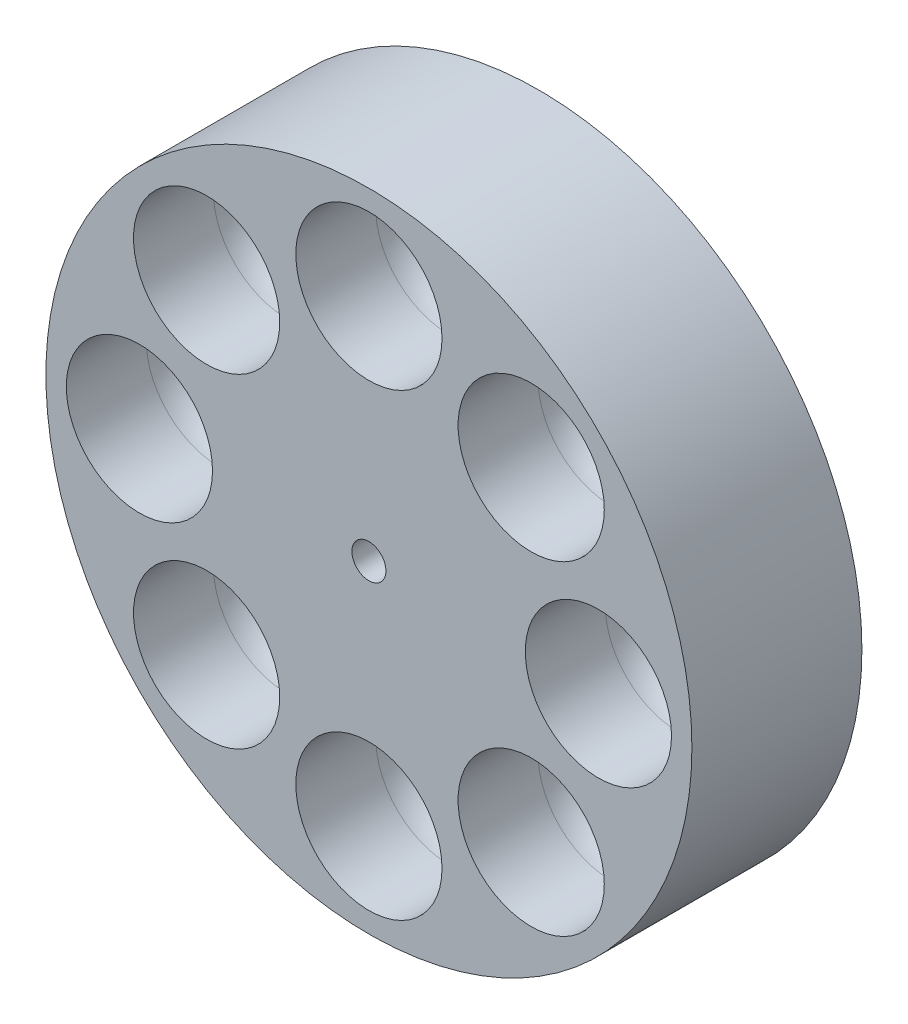
SolidWorks part; units mm, degrees
ref_plane "Front Plane" through (0, 0, 0) normal (0, 0, 1) x (1, 0, 0)
ref_plane "Top Plane" through (0, 0, 0) normal (0, 1, 0) x (1, 0, 0)
ref_plane "Right Plane" through (0, 0, 0) normal (1, 0, 0) x (0, 0, -1)
sketch "Sketch1" plane through (0, 0, 0) normal (0, 0, 1) x (1, 0, 0)
  circle A0 centre (0, 0) radius 19
  circle A1 centre (0, 0) radius 1
  dimension "D1" = 2
  dimension "D2" = 38
extrude "Boss-Extrude1" add sketch "Sketch1" along normal blind 10
sketch "Sketch2" plane through (0, 0, 10) normal (0, 0, 1) x (1, 0, 0)
  circle A0 centre (0, 13.5) radius 4.3
  circle A1 centre (9.5459, 9.5459) radius 4.3
  circle A2 centre (13.5, 0) radius 4.3
  circle A3 centre (9.5459, -9.5459) radius 4.3
  circle A4 centre (0, -13.5) radius 4.3
  circle A5 centre (-9.5459, -9.5459) radius 4.3
  circle A6 centre (-13.5, 0) radius 4.3
  circle A7 centre (-9.5459, 9.5459) radius 4.3
  point P19 (0, 0)
  dimension "D2" = 8.6
  dimension "D1" = 13.5
  dimension "D3" = 8
extrude "Cut-Extrude1" cut sketch "Sketch2" against normal offset from surface (9 mm away) 1 up to face at (19, 0, 0)
fillet "Fillet1" radius 4.3 8 edges at (-5.2459, -9.5459, 1) (4.3, -13.5, 1) (13.8459, -9.5459, 1) (17.8, 0, 1) (13.8459, 9.5459, 1) (4.3, 13.5, 1) (-9.2, 0, 1) (-5.2459, 9.5459, 1)
